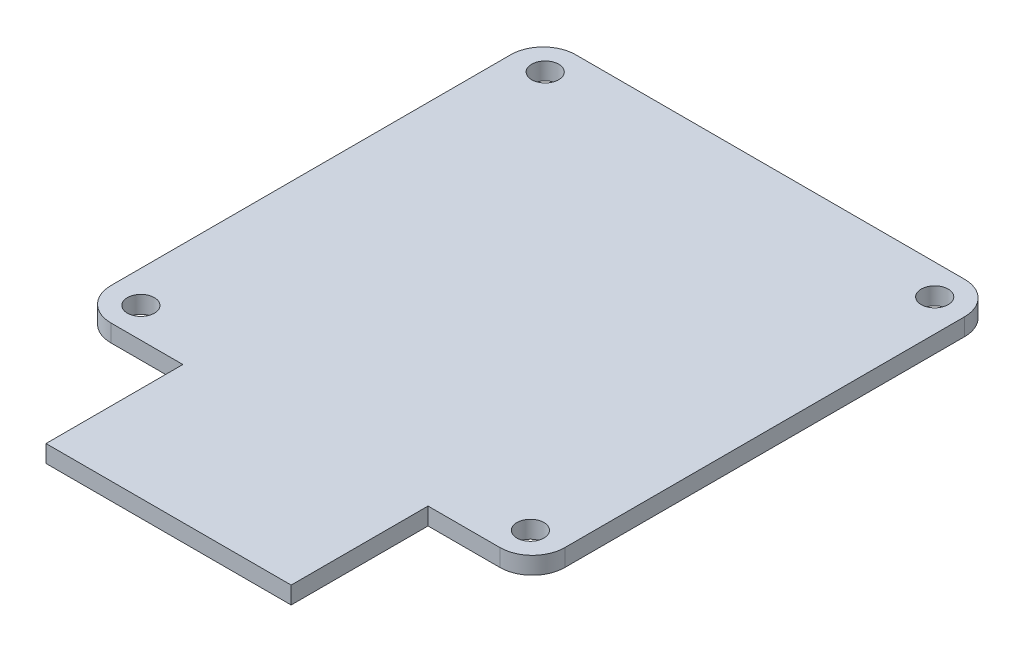
SolidWorks part; units mm, degrees
ref_plane "Front Plane" through (0, 0, 0) normal (0, 0, 1) x (1, 0, 0)
ref_plane "Top Plane" through (0, 0, 0) normal (0, 1, 0) x (1, 0, 0)
ref_plane "Right Plane" through (0, 0, 0) normal (1, 0, 0) x (0, 0, -1)
sketch "Sketch1" plane through (0, 0, 0) normal (0, 1, 0) x (1, 0, 0)
  line L1 (-18, 21.5) -> (18, 21.5)
  line L2 (-21, 18.5) -> (-21, -18.5)
  line L3 (-18, -21.5) -> (18, -21.5)
  line L4 (21, 18.5) -> (21, -18.5)
  line L5 (-21, 21.5) -> (21, -21.5) construction
  line L6 (-21, -21.5) -> (21, 21.5) construction
  line L7 (18.0215, -18.707) -> (-18.0215, -18.707) construction
  line L8 (18.0215, -18.707) -> (18.0215, 18.707) construction
  line L9 (18.0215, 18.707) -> (-18.0215, 18.707) construction
  line L10 (-18.0215, -18.707) -> (-18.0215, 18.707) construction
  line L11 (18.0215, -18.707) -> (-18.0215, 18.707) construction
  line L12 (18.0215, 18.707) -> (-18.0215, -18.707) construction
  line L13 (-11.3434, -21.5) -> (11.3434, -21.5)
  line L14 (-11.3434, -21.5) -> (-11.3434, -34.1662)
  line L15 (-11.3434, -34.1662) -> (11.3434, -34.1662)
  line L16 (11.3434, -21.5) -> (11.3434, -34.1662)
  circle A0 centre (0, 0) radius 36 construction
  circle A1 centre (-18.0215, 18.707) radius 1.25
  circle A2 centre (18.0215, 18.707) radius 1.25
  circle A3 centre (18.0215, -18.707) radius 1.25
  circle A4 centre (-18.0215, -18.707) radius 1.25
  arc A5 (18, -21.5) -> (21, -18.5) centre (18, -18.5) ccw
  arc A6 (-21, -18.5) -> (-18, -21.5) centre (-18, -18.5) ccw
  arc A7 (18, 21.5) -> (21, 18.5) centre (18, 18.5) cw
  arc A8 (-18, 21.5) -> (-21, 18.5) centre (-18, 18.5) ccw
  point P0 (0, 0)
  point P32 (0, 0)
  point P33 (0, 0)
  point P34 (-11.3434, -34.1662)
  dimension "D3" = 72
  dimension "D4" = 2.5
  dimension "D7" = 3
  dimension "D1" = 42
  dimension "D2" = 43
  dimension "D5" = 36.043
  dimension "D6" = 37.414
extrude "Boss-Extrude1" add sketch "Sketch1" along normal blind 1.6 contours L1 A8 L2 A6 L3 A5 L4 A7 A1 A2 A3 A4 | L16 L3 L14 L15 region at (0, 0, 0) region at (0, 0, 27.8331)
ref_axis "Axis1" through (0, -0.08, 0) along (0, 1, 0)
